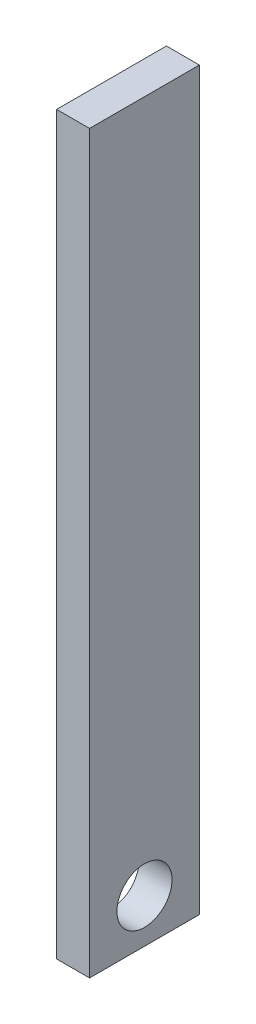
SolidWorks part; units mm, degrees
material "C-Glass Fiber"
ref_plane "xy_plane" through (0, 0, 0) normal (0, 0, 1) x (1, 0, 0)
ref_plane "zx_plane" through (0, 0, 0) normal (0, 1, 0) x (1, 0, 0)
ref_plane "yz_plane" through (0, 0, 0) normal (1, 0, 0) x (0, 0, -1)
ref_axis "x_axis" through (-80.9, 0, 0) along (1, 0, 0)
ref_axis "y_axis" through (0, -50, 0) along (0, 1, 0)
ref_axis "z_axis" through (0, 0, -80.9) along (0, 0, 1)
ref_plane "xMid_plane" through (0, 0, 0) normal (1, 0, 0) x (0, 0, -1)
ref_plane "xMin_plane" through (-1.5, 0, 0) normal (1, 0, 0) x (0, 0, -1)
ref_plane "xMax_plane" through (1.5, 0, 0) normal (1, 0, 0) x (0, 0, -1)
ref_plane "yMid_plane" through (0, 0, 0) normal (0, 1, 0) x (1, 0, 0)
ref_plane "yMin_plane" through (0, -33.5, 0) normal (0, 1, 0) x (1, 0, 0)
ref_plane "yMax_plane" through (0, 33.5, 0) normal (0, 1, 0) x (1, 0, 0)
ref_plane "zMid_plane" through (0, 0, 0) normal (0, 0, 1) x (1, 0, 0)
ref_plane "zMin_plane" through (0, 0, -5) normal (0, 0, 1) x (1, 0, 0)
ref_plane "zMax_plane" through (0, 0, 5) normal (0, 0, 1) x (1, 0, 0)
sketch "projectionXy_sketch" plane through (0, 0, 0) normal (0, 0, 1) x (1, 0, 0)
  line L0 (55, 33.5) -> (-55, 33.5) construction
  line L1 (-1.5, 33.5) -> (1.5, 33.5)
  line L2 (-1.5, 33.5) -> (-1.5, -33.5)
  line L3 (-1.5, -33.5) -> (1.5, -33.5)
  line L4 (1.5, 33.5) -> (1.5, -33.5)
  line L5 (55, -33.5) -> (-55, -33.5) construction
  line L6 (1.5, -55) -> (1.5, 55) construction
  line L7 (-1.5, -55) -> (-1.5, 55) construction
extrude "mainBody_extrude" add sketch "projectionXy_sketch" along normal up to surface (5 mm away) from surface up to plane "zMax_plane" starting at plane "zMin_plane"
sketch3d "pivotTargetRootPoint_sketch"
  point P0 (0, -29.5, 0)
  dimension "D1" = 4
ref_point "pivotTargetRootPoint"
ref_axis "pivotTarget_axis" through (0, -29.5, 0) along (1, 0, 0)
sketch "pivotShaftHole_sketch" plane through (0, 0, 0) normal (1, 0, 0) x (0, 0, -1)
  circle A0 centre (0, -29.5) radius 2.51
  point P2 (0, 0)
  dimension "D1" = 5.02
extrude "pivotShaftHole_cut" cut sketch "pivotShaftHole_sketch" against normal through all both and the other way through all from surface starting at plane "xMid_plane"
equation "\"D1@xMin_plane\"= \"externalParameters.this.extentX\" / 2"
equation "\"D1@xMax_plane\" = \"externalParameters.this.extentX\" / 2"
equation "\"D1@yMin_plane\" = \"externalParameters.this.extentY\" / 2"
equation "\"D1@yMax_plane\" = \"externalParameters.this.extentY\" / 2"
equation "\"D1@zMin_plane\" = \"externalParameters.this.extentZ\" / 2"
equation "\"D1@zMax_plane\" = \"externalParameters.this.extentZ\" / 2"
equation "\"D1@pivotTargetRootPoint_sketch\"=\"externalParameters.this.pivotDedendum\""
equation "\"D1@pivotShaftHole_sketch\"=\"externalParameters.pivotShaft.holeDiameter\""
